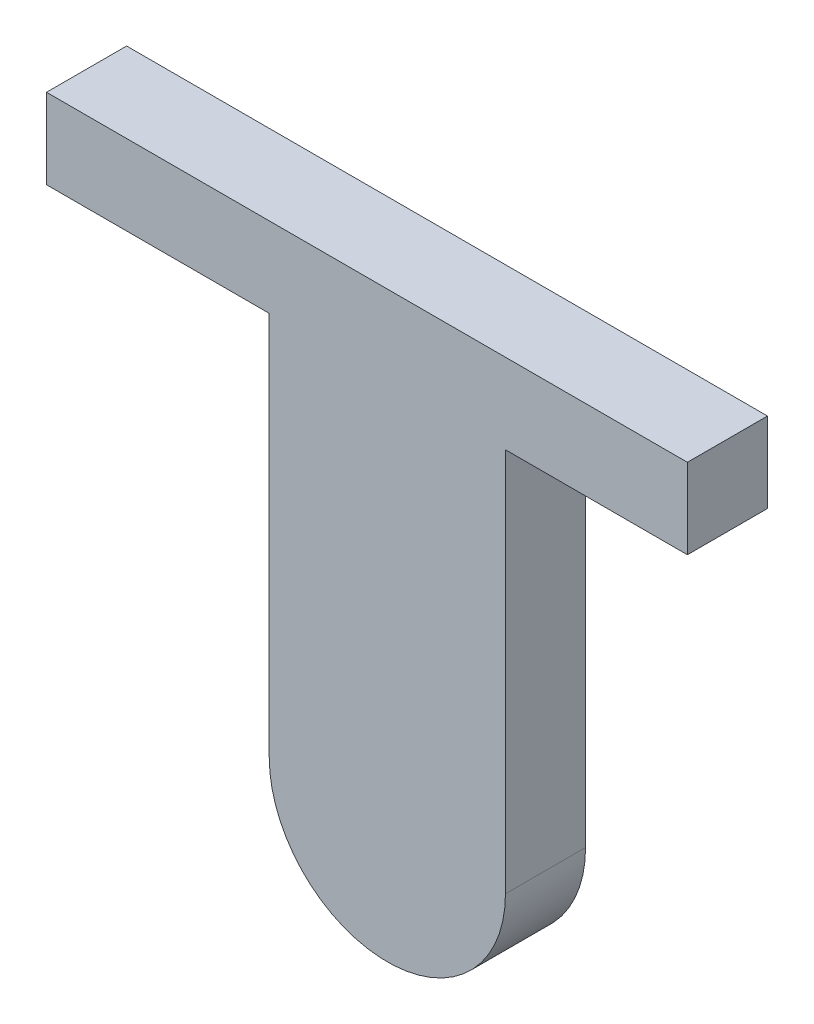
SolidWorks part; units mm, degrees
ref_plane "Front Plane" through (0, 0, 0) normal (0, 0, 1) x (1, 0, 0)
ref_plane "Top Plane" through (0, 0, 0) normal (0, 1, 0) x (1, 0, 0)
ref_plane "Right Plane" through (0, 0, 0) normal (1, 0, 0) x (0, 0, -1)
sketch "Sketch1" plane through (0, 0, 0) normal (0, 0, 1) x (1, 0, 0)
  line L0 (-28.1963, 45.4833) -> (51.8037, 45.4833)
  line L1 (-28.1963, 45.4833) -> (-28.1963, 35.4833)
  line L2 (-28.1963, 35.4833) -> (-0.3931, 35.4833)
  line L3 (51.8037, 45.4833) -> (51.8037, 35.4833)
  line L4 (51.8037, 35.4833) -> (29.0941, 35.4833)
  line L5 (-0.3931, 35.4833) -> (-0.3931, -12.5167)
  line L6 (29.0941, 35.4833) -> (29.0941, -12.5167)
  line L8 (23.1035, 0) -> (5.1035, 0)
  line L9 (23.1035, 0) -> (23.1035, -24.3809)
  line L10 (5.1035, 0) -> (5.1035, -24)
  line L11 (14.3505, 49.9292) -> (14.3505, -27.2603) construction
  arc A0 (-0.3931, -12.5167) -> (29.0941, -12.5167) centre (14.3505, -12.5167) ccw
  circle A1 centre (14.3505, -12.5167) radius 6.5
  circle A4 centre (-88.0417, 23.4793) radius 1.2349
  dimension "D6" = 13
  dimension "D1" = 80
  dimension "D2" = 10
  dimension "D3" = 48
  dimension "D4" = 24
  dimension "D5" = 18
extrude "Boss-Extrude1" add sketch "Sketch1" along normal blind 10 contours L2 L5 A0 L6 L4 L3 L0 L1
